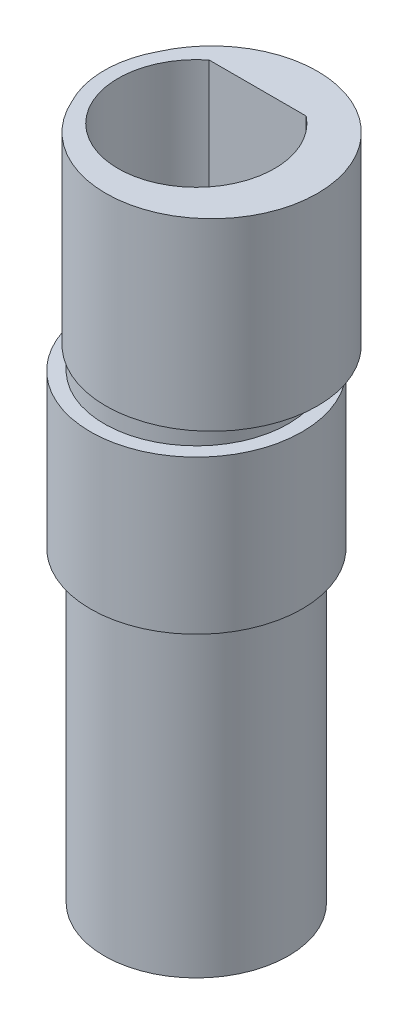
SolidWorks part; units mm, degrees
ref_plane "Front Plane" through (0, 0, 0) normal (0, 0, 1) x (1, 0, 0)
ref_plane "Top Plane" through (0, 0, 0) normal (0, 1, 0) x (1, 0, 0)
ref_plane "Right Plane" through (0, 0, 0) normal (1, 0, 0) x (0, 0, -1)
sketch "Sketch1" plane through (0, 0, 0) normal (0, 1, 0) x (1, 0, 0)
  circle A0 centre (0, 0) radius 3.45
  dimension "D1" = 6.9
extrude "Boss-Extrude1" add sketch "Sketch1" along normal blind 6
sketch "Sketch2" plane through (0, -4.98, 0) normal (0, -1, 0) x (1, 0, 0)
  line L0 (0, 0) -> (-0.5, 0) construction
  circle A0 centre (-0.5, 0) radius 3.45
  dimension "D1" = 6.9
extrude "Boss-Extrude2" add sketch "Sketch2" against normal blind 4 and the other way blind 1
sketch "Sketch3" plane through (0, 6, 0) normal (0, 1, 0) x (1, 0, 0)
  circle A0 centre (-0.5, 0) radius 3
  dimension "D1" = 6
extrude "Boss-Extrude4" add sketch "Sketch3" against normal blind 22
sketch "Sketch4" plane through (0, -16, 0) normal (0, -1, 0) x (1, 0, 0)
  line L0 (0, 0) -> (-0.5, 0)
  circle A0 centre (-0.5, 0) radius 2.55
  dimension "D1" = 5.1
extrude "Cut-Extrude1" cut sketch "Sketch4" against normal through all contours A0
sketch "Sketch5" plane through (0, 6, 0) normal (0, 1, 0) x (1, 0, 0)
  line L2 (1.0819, 2) -> (-2.0819, 2)
  circle A0 centre (-0.5, 0) radius 2.55 construction
  circle A1 centre (-0.5, 0) radius 2.55
  circle M3 centre (-0.5, 0) radius 2.55
extrude "Boss-Extrude5" add sketch "Sketch5" against normal blind 12.8 contours L2 M3 region at (-0.5, 6, -2.2222)
